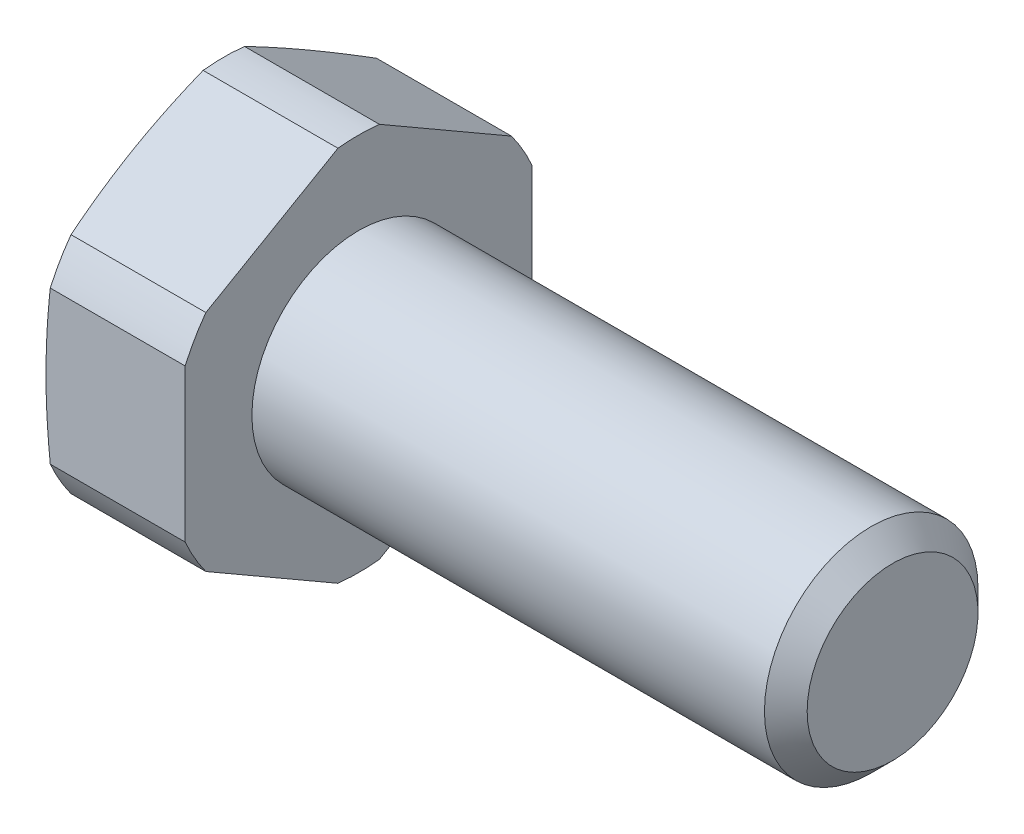
SolidWorks part; units mm, degrees
material "AISI 1020"
ref_plane "Спереди" through (0, 0, 0) normal (0, 0, 1) x (1, 0, 0)
ref_plane "Сверху" through (0, 0, 0) normal (0, 1, 0) x (1, 0, 0)
ref_plane "Справа" through (0, 0, 0) normal (1, 0, 0) x (0, 0, -1)
sketch "Эскиз1" plane through (0, 0, 0) normal (0, 0, 1) x (1, 0, 0)
  line L0 (-1000, 0) -> (49000, 0) construction
  line L1 (-5.3, 0) -> (-5.3, 6.175)
  line L2 (-5.3, 6.175) -> (-5.0521, 7.1)
  line L3 (-5.0521, 7.1) -> (0, 7.1)
  line L4 (0, 7.1) -> (0, 4)
  line L5 (0, 4) -> (19.2, 4)
  line L6 (20, 3.2) -> (20, 0)
  line L7 (20, 4) -> (20.625, 5.0825) construction
  line L8 (20.625, 5.0825) -> (21.25, 4) construction
  line L9 (21.25, 4) -> (20, 4) construction
  line L10 (20.625, 5.0825) -> (20.625, 4) construction
  line L11 (20.625, 5.0825) -> (0.625, 5.0825) construction
  line L12 (19.2, 4) -> (20, 3.2)
  line L13 (20, 4) -> (19.6, 3.6) construction
  line L14 (-5.3, 6.175) -> (-18.3, 6.175) construction
  line L15 (-5.3, 0) -> (20, 0)
  dimension "D2" = 15
revolve "Повернуть1" add sketch "Эскиз1" angle 360 about L0
cosmetic thread "Условное изображение резьбы1" parameters "D1"=20, "D2"=5.8349
sketch "Эскиз2" plane through (-5.3, 0, 0) normal (-1, 0, 0) x (0, 0, 1)
  line L1 (0, 7.5056) -> (-6.5, 3.7528)
  line L2 (-6.5, 3.7528) -> (-6.5, -3.7528)
  line L3 (-6.5, -3.7528) -> (0, -7.5056)
  line L4 (0, -7.5056) -> (6.5, -3.7528)
  line L5 (6.5, -3.7528) -> (6.5, 3.7528)
  line L6 (6.5, 3.7528) -> (0, 7.5056)
  circle A0 centre (0, 0) radius 6.5 construction
extrude "Вырез-Вытянуть1" cut sketch "Эскиз2" against normal up to surface (25.3 mm away) flip side to cut up to face at (20, 0, 3.2)
equation "\"D1@Эскиз1\"=\"_d_@Эскиз1\"/10"
equation "\"D@Эскиз1\"=\"S_@Эскиз1\"*0.95"
equation "\"D1@Эскиз2\"=\"S_@Эскиз1\""
equation "\"D1@Условное изображение резьбы1\"=\"b_@Эскиз1\""
equation "\"D2@Условное изображение резьбы1\"=\"_d_@Эскиз1\"-\"dr@Эскиз1\"*2"
